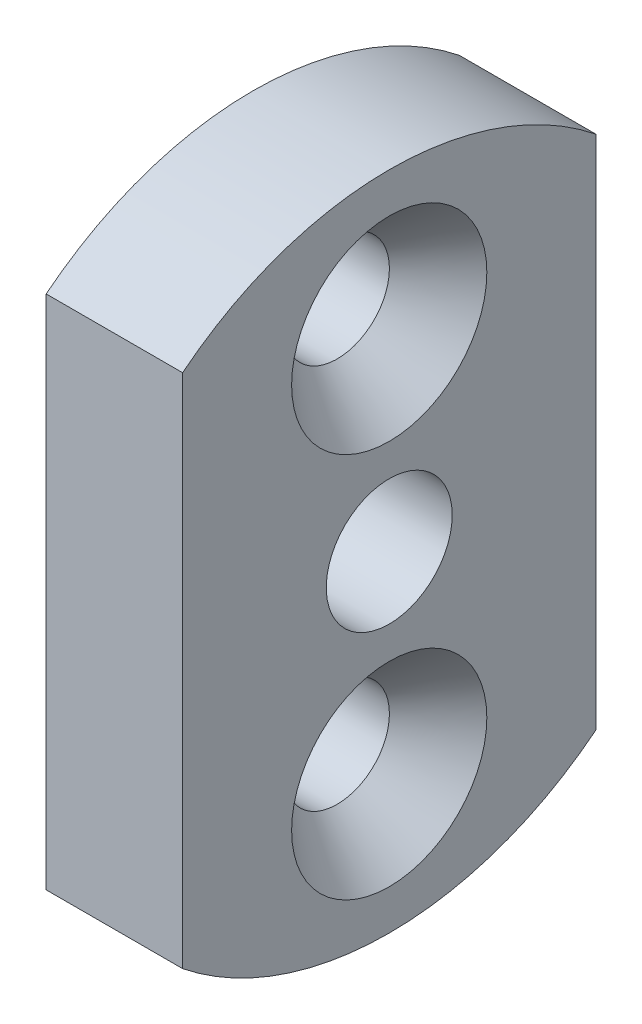
SolidWorks part; units mm, degrees
material "Beech"
ref_plane "Front" through (0, 0, 0) normal (0, 0, 1) x (1, 0, 0)
ref_plane "Top" through (0, 0, 0) normal (0, 1, 0) x (1, 0, 0)
ref_plane "Right" through (0, 0, 0) normal (1, 0, 0) x (0, 0, -1)
ref_axis "side-side" through (80.9, 0, 0) along (-1, 0, 0)
ref_axis "up-down" through (0, 50, 0) along (0, -1, 0)
ref_axis "front-back" through (0, 0, -80.9) along (0, 0, 1)
sketch "Sketch1" plane through (0, 0, 0) normal (1, 0, 0) x (0, 0, -1)
  line L0 (0, 0) -> (-24.1267, 0) construction
  line L1 (-7.5, 9.3675) -> (7.5, -9.3675) construction
  line L2 (-7.5, 9.3675) -> (7.5, 9.3675) construction
  line L3 (-7.5, 9.3675) -> (-7.5, -9.3675)
  line L4 (-7.5, -9.3675) -> (7.5, -9.3675) construction
  line L5 (7.5, 9.3675) -> (7.5, -9.3675)
  circle A0 centre (0, 0) radius 12 construction
  circle A1 centre (0, 7) radius 1.7272
  circle A2 centre (0, -7) radius 1.7272
  circle A3 centre (0, 0) radius 2.286
  arc A4 (-7.5, 9.3675) -> (7.5, 9.3675) centre (0, 0) cw
  arc A5 (-7.5, -9.3675) -> (7.5, -9.3675) centre (0, 0) ccw
  dimension "D1" = 3.4544
  dimension "D2" = 24
  dimension "D3" = 14
  dimension "D4" = 4.572
  dimension "D5" = 15
  dimension "D6" = 18.735
extrude "Boss-Extrude1" add sketch "Sketch1" along normal blind 4.953
hole_wizard "CSK for #6 Flat Head Machine Screw1" positions "Sketch2" profile "Sketch3" countersink size "#6" standard "ANSI Inch"
sketch "Sketch2" plane through (4.953, 0, 0) normal (1, 0, 0) x (0, 0, -1)
  circle A0 centre (0, -7) radius 1.7272 construction
  point P0 (0, -7)
  point P2 (0, 7)
  point P5 (0, 0)
sketch "Sketch3" plane through (4.953, -7, 0) normal (0, 1, 0) x (0, 0, -1)
  line L0 (0, 0) -> (0, 12.1138)
  line L1 (0, 12.1138) -> (1.8986, 10.973)
  line L2 (1.8986, 10.973) -> (1.8986, 1.892)
  line L3 (1.8986, 1.892) -> (3.5433, 0)
  line L5 (3.5433, 0) -> (0, 0)
  line L6 (-1.8986, 1.892) -> (-3.5433, 0) construction
  line L10 (0, 12.1138) -> (-1.8987, 10.973) construction
  line L11 (0, -6.35) -> (0, 107.95) construction
  dimension "Hole Dia." = 3.7973
  dimension "Hole Depth" = 10.973
  dimension "Near C'Sink Dia." = 7.0866
  dimension "Near C'Sink Angle" = 82
  dimension "Drill Angle" = 118
